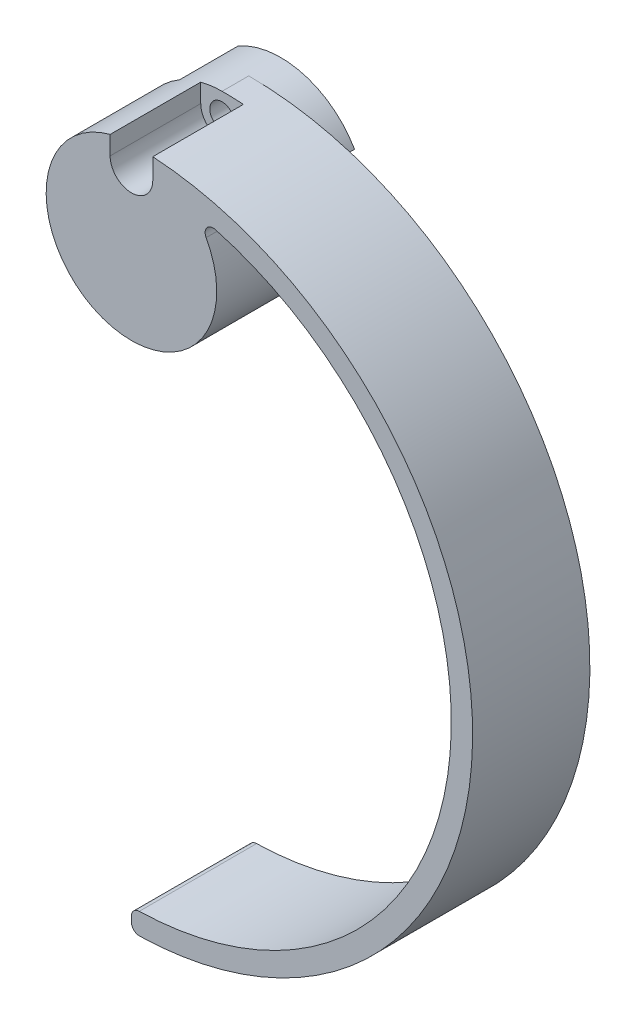
SolidWorks part; units mm, degrees
ref_plane "Front Plane" through (0, 0, 0) normal (0, 0, 1) x (1, 0, 0)
ref_plane "Top Plane" through (0, 0, 0) normal (0, 1, 0) x (1, 0, 0)
ref_plane "Right Plane" through (0, 0, 0) normal (1, 0, 0) x (0, 0, -1)
sketch "Leg-Sketch" plane through (0, 0, 0) normal (0, 0, 1) x (1, 0, 0)
  line L0 (0, 0) -> (0, -56) construction
  line L1 (0, -56) -> (0, -54)
  circle A0 centre (0, 0) radius 8 construction
  circle A1 centre (0, 0) radius 6 construction
  circle A2 centre (0, 6) radius 1.15
  circle A3 centre (-6, 0) radius 1.15
  circle A4 centre (0, -6) radius 1.15
  circle A5 centre (6, 0) radius 1.15
  arc A6 (0, 8) -> (0, -8) centre (0, 0) ccw
  arc A7 (0, 8) -> (0, -56) centre (0, -24) cw
  arc A8 (5.8873, 5.4167) -> (0, -54) centre (0, -24) cw
  arc A9 (0, -8) -> (5.8873, 5.4167) centre (0, 0) ccw
  point P12 (0, 8)
  dimension "D1" = 16
  dimension "D2" = 12
  dimension "D3" = 2.3
  dimension "D4" = 2
  dimension "D5" = 64
extrude "Leg" add sketch "Leg-Sketch" along normal blind 11
sketch "Hub-Sketch" plane through (0, 0, 0) normal (0, 0, -1) x (-1, 0, 0)
  circle A0 centre (0, 0) radius 8
  circle A1 centre (0, 6) radius 1.15 construction
  circle A2 centre (-6, 0) radius 1.15 construction
  circle A3 centre (0, -6) radius 1.15 construction
  circle A4 centre (6, 0) radius 1.15 construction
  circle A5 centre (0, 6) radius 1.15
  circle A6 centre (-6, 0) radius 1.15
  circle A7 centre (0, -6) radius 1.15
  circle A8 centre (6, 0) radius 1.15
extrude "Hub" add sketch "Hub-Sketch" along normal blind 3
sketch "Clearance-Sketch" plane through (0, 0, 11) normal (0, 0, 1) x (1, 0, 0)
  line L0 (6, 2) -> (8, 2)
  line L1 (8, 2) -> (8, -2)
  line L2 (8, -2) -> (6, -2)
  line L3 (2, -6) -> (2, -8)
  line L4 (2, -8) -> (-2, -8)
  line L5 (-2, -8) -> (-2, -6)
  line L6 (-6, -2) -> (-8, -2)
  line L7 (-8, -2) -> (-8, 2)
  line L8 (-8, 2) -> (-6, 2)
  line L9 (-2, 6) -> (-2, 8)
  line L10 (-2, 8) -> (2, 8)
  line L11 (2, 8) -> (2, 6)
  circle A0 centre (6, 0) radius 2 construction
  circle A1 centre (0, 6) radius 2 construction
  circle A2 centre (-6, 0) radius 2 construction
  circle A3 centre (0, -6) radius 2 construction
  arc A4 (2, 6) -> (-2, 6) centre (0, 6) cw
  arc A5 (-6, 2) -> (-6, -2) centre (-6, 0) cw
  arc A6 (-2, -6) -> (2, -6) centre (0, -6) cw
  arc A7 (6, -2) -> (6, 2) centre (6, 0) cw
  circle A8 centre (0, 0) radius 8 construction
  dimension "D1" = 4
extrude "Clearance" cut sketch "Clearance-Sketch" against normal offset from surface (8.5 mm away) 5.5 up to face at (-1.15, -6, -3)
sketch "Hub-Cutout-Sketch" plane through (0, 0, -3) normal (0, 0, -1) x (-1, 0, 0)
  line L0 (-3.4208, 1.975) -> (-6.9282, 4)
  line L1 (4, 6.9282) -> (1.975, 3.4208)
  line L7 (2.0172, -3.3961) -> (2.7243, -4.1032)
  line L8 (2.7243, -4.1032) -> (4.1032, -2.7243)
  line L9 (4.1032, -2.7243) -> (3.3961, -2.0172)
  line L10 (0, 0) -> (2.3478, 0) construction
  circle A1 centre (0, 0) radius 8 construction
  arc A2 (-6.9282, 4) -> (4, 6.9282) centre (0, 0) ccw
  arc A3 (-3.4208, 1.975) -> (2.0172, -3.3961) centre (0, 0) ccw
  arc A4 (3.3961, -2.0172) -> (1.975, 3.4208) centre (0, 0) ccw
  dimension "D2" = 3.95
  dimension "D1" = 90
  dimension "D3" = 45
  dimension "D4" = 1
  dimension "D5" = 1.95
  dimension "D6" = 30
extrude "Hub-Cutout" cut sketch "Hub-Cutout-Sketch" against normal up to surface (5.5 mm away) up to face at (4.85, 0, 2.5)
sketch "Cover-Bolts-Sketch" plane through (0, 0, 11) normal (0, 0, 1) x (1, 0, 0)
  line L0 (5.6569, 5.6569) -> (0, 0)
  line L1 (0, 0) -> (-5.6569, 5.6569)
  arc A0 (-5.6569, 5.6569) -> (5.6569, 5.6569) centre (0, 0) ccw
  arc A1 (-2, 7.746) -> (-7.746, 2) centre (0, 0) ccw construction
extrude "Cover-Bolts" add sketch "Cover-Bolts-Sketch" against normal offset from surface (6 mm away) 2.5 up to face at (-0.3679, -1.2187, 2.5)
fillet "Fillet" radius 0.75 3 edges at (5.8873, 5.4167, 5.5) (0, -56, 5.5) (0, -54, 5.5)
mirror "Mirror" [suppressed] about plane through (0, 0, 0) normal (0, 0, 1) of bodies 106
delete or keep bodies "KeepMirrorBody" [suppressed] type keep bodies bodies 108
equation "\"D1@Hub\" = \"HUB_WIDTH\""
equation "\"LEG_CLEARANCE\"= 3mm"
equation "\"LEG_WIDTH\"= 11mm"
equation "\"LEG_THICKNESS\"= 1.6mm"
equation "\"LEG_DIAMETER\"= 64mm"
equation "\"HUB_WIDTH\" = \"LEG_CLEARANCE\""
equation "\"D5@Leg-Sketch\" = \"LEG_DIAMETER\""
equation "\"D4@Leg-Sketch\" = \"LEG_THICKNESS\""
equation "\"D1@Leg\"=\"LEG_WIDTH\""
